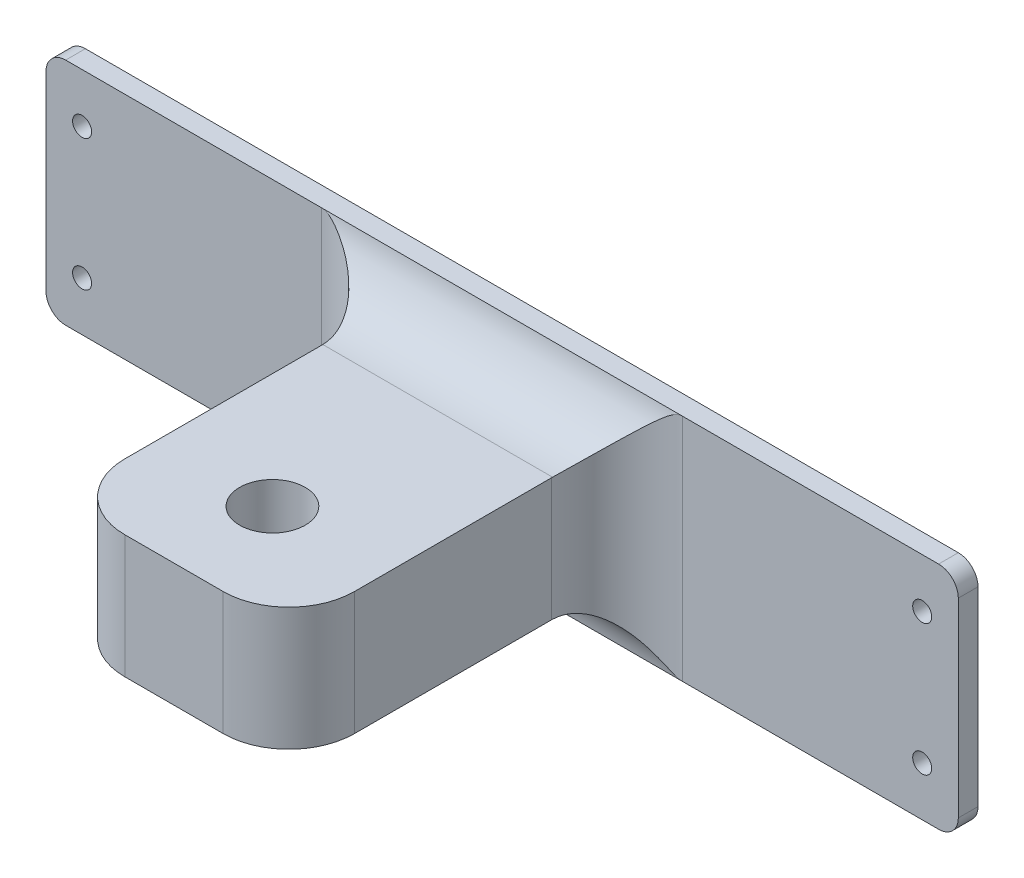
SolidWorks part; units mm, degrees
ref_plane "Plan de face" through (0, 0, 0) normal (0, 0, 1) x (1, 0, 0)
ref_plane "Plan de dessus" through (0, 0, 0) normal (0, 1, 0) x (1, 0, 0)
ref_plane "Plan de droite" through (0, 0, 0) normal (1, 0, 0) x (0, 0, -1)
sketch "Esquisse7" plane through (0, 0, 0) normal (0, 0, 1) x (1, 0, 0)
  line L1 (69.5, -17.5) -> (-69.5, -17.5)
  line L2 (69.5, -17.5) -> (69.5, 17.5)
  line L3 (69.5, 17.5) -> (-69.5, 17.5)
  line L4 (-69.5, -17.5) -> (-69.5, 17.5)
  line L5 (69.5, -17.5) -> (-69.5, 17.5) construction
  line L6 (69.5, 17.5) -> (-69.5, -17.5) construction
  point P0 (0, 0)
  point P6 (0, 0)
  dimension "D1" = 35
  dimension "D2" = 139
extrude "Boss.-Extru.1" add sketch "Esquisse7" against normal blind 3
sketch "Esquisse8" plane through (0, 0, 0) normal (0, 0, 1) x (1, 0, 0)
  line L0 (-69.5, -17.5) -> (69.5, -17.5) construction
  line L5 (-18.3284, 17.5) -> (18.3284, -17.5) construction
  line L6 (0, -20.019) -> (0, 20.019) construction
  line L8 (-17.5, 9.375) -> (17.5, 9.375)
  line L9 (-17.5, 9.375) -> (-17.5, -9.375)
  line L10 (-17.5, -9.375) -> (17.5, -9.375)
  line L11 (17.5, 9.375) -> (17.5, -9.375)
  line L12 (-17.5, 9.375) -> (17.5, -9.375) construction
  line L13 (-17.5, -9.375) -> (17.5, 9.375) construction
  point P0 (0, 0)
  point P8 (0, 0)
  dimension "D1" = 18.75
  dimension "D2" = 35
extrude "Boss.-Extru.2" add sketch "Esquisse8" along normal blind 50
sketch "Esquisse9" plane through (0, -9.375, 0) normal (0, -1, 0) x (-1, 0, 0)
  line L0 (17.5, 0) -> (-17.5, 0) construction
  circle A0 centre (0, -35) radius 5
  dimension "D1" = 35
  dimension "D2" = 10
fillet "Congé1" radius 10 6 edges at (0, -9.375, 0) (0, 9.375, 0) (17.5, 0, 0) (-17.5, 0, 0) (-17.5, 0, 50) (17.5, 0, 50)
sketch "Esquisse14" plane through (0, 0, 0) normal (0, 0, 1) x (1, 0, 0)
  line L1 (-64, -10) -> (64, -10)
  line L2 (-64, -10) -> (-64, 10)
  line L3 (-64, 10) -> (64, 10)
  line L4 (64, -10) -> (64, 10)
  line L5 (-64, -10) -> (64, 10) construction
  line L6 (-64, 10) -> (64, -10) construction
  point P1 (0, 0)
  dimension "D1" = 128
  dimension "D2" = 20
hole_wizard "Dégagement M2.52" positions "Esquisse17" profile "Esquisse18" hole size "M2.5" standard "Ansi Metric" end condition up to next
sketch "Esquisse17" plane through (0, 0, 0) normal (0, 0, 1) x (1, 0, 0)
  point P0 (64, -10)
  point P3 (64, 10)
  point P6 (-64, -10)
  point P9 (-64, 10)
sketch "Esquisse18" plane through (64, -10, 0) normal (1, 0, 0) x (0, -1, 0)
  line L0 (0, 0) -> (0, 3)
  line L1 (0, 3) -> (1.45, 3)
  line L2 (1.45, 3) -> (1.45, 0)
  line L5 (1.45, 0) -> (0, 0)
  line L11 (0, -6.35) -> (0, 107.95) construction
  dimension "Diamètre du perçage jusqu'au prochain" = 2.9
  dimension "Profondeur du perçage jusqu'au prochain" = 3
extrude "Enlèv. mat.-Extru.2" cut sketch "Esquisse9" against normal through all contours A0
fillet "Congé2" radius 3 4 edges at (-69.5, 17.5, -1.5) (-69.5, -17.5, -1.5) (69.5, 17.5, -1.5) (69.5, -17.5, -1.5)
